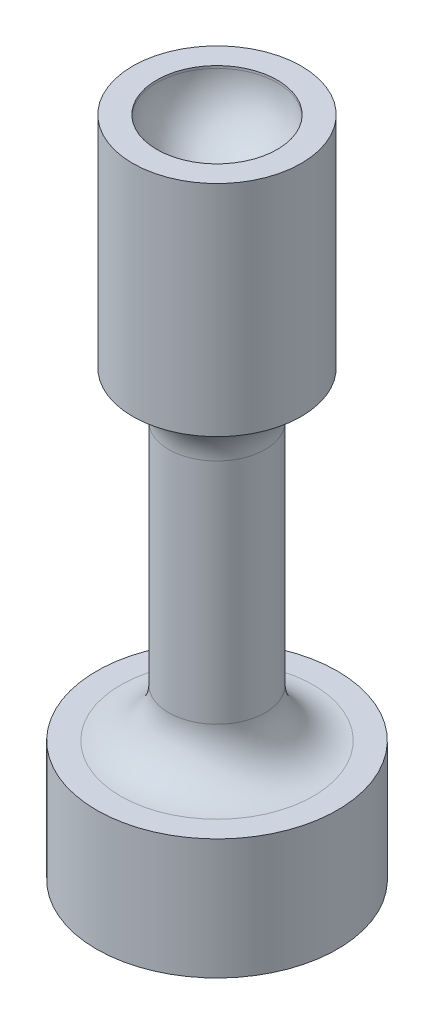
SolidWorks part; units mm, degrees
ref_plane "Front Plane" through (0, 0, 0) normal (0, 0, 1) x (1, 0, 0)
ref_plane "Top Plane" through (0, 0, 0) normal (0, 1, 0) x (1, 0, 0)
ref_plane "Right Plane" through (0, 0, 0) normal (1, 0, 0) x (0, 0, -1)
sketch "Sketch1" plane through (0, 0, 0) normal (0, 1, 0) x (1, 0, 0)
  circle A0 centre (0, 0) radius 5
  dimension "D1" = 10
extrude "Boss-Extrude1" add sketch "Sketch1" along normal blind 27.5
sketch "Sketch2" plane through (0, 0, 0) normal (0, -1, 0) x (1, 0, 0)
  line L1 (-2.0543, 3.4804) -> (-4.0413, -0.0388)
  line L2 (-4.0413, -0.0388) -> (-1.987, -3.5193)
  line L3 (-1.987, -3.5193) -> (2.0543, -3.4804)
  line L4 (2.0543, -3.4804) -> (4.0413, 0.0388)
  line L5 (4.0413, 0.0388) -> (1.987, 3.5193)
  line L6 (1.987, 3.5193) -> (-2.0543, 3.4804)
  circle A0 centre (0, 0) radius 3.5 construction
  dimension "D1" = 7
sketch "Sketch11" plane through (0, 27.5, 0) normal (0, 1, 0) x (1, 0, 0)
  circle A0 centre (0, 0) radius 2.5
  dimension "D1" = 5
extrude "Cut-Extrude3" cut sketch "Sketch11" against normal blind 0.1 contours A0
dome "Dome2" faces to dome 1 distance 2.5 reverse direction yes elliptical dome yes face at (0, 27.4, 2.5) parameters "D1"=2.5
sketch "Sketch12" plane through (0, 27.5, 0) normal (0, 1, 0) x (1, 0, 0)
  circle A0 centre (0, 0) radius 3.5
  circle A3 centre (0, 0) radius 5
  circle A4 centre (0, 0) radius 5
  dimension "D1" = 7
  dimension "D2" = 0
extrude "Cut-Extrude4" cut sketch "Sketch12" against normal blind 22.5
extrude "Cut-Extrude5" cut sketch "Sketch2" against normal blind 3
sketch "Sketch14" plane through (0, 0, 0) normal (0, 0, 1) x (1, 0, 0)
  line L0 (3.5, 5) -> (3.5, 27.5) construction
  line L1 (2, 5) -> (5, 5)
  line L2 (2, 5) -> (2, 18.4)
  line L3 (2, 18.4) -> (5, 18.4)
  line L4 (5, 5) -> (5, 18.4)
  line L5 (2, 5) -> (5, 18.4) construction
  line L6 (2, 18.4) -> (5, 5) construction
  line L7 (5, 5) -> (-5, 5) construction
  line L8 (0, 0) -> (0, 27.5) construction
  line L9 (2.5, 27.5) -> (-2.5, 27.5) construction
  point P0 (3.5, 11.7)
  dimension "D1" = 13.4
  dimension "D2" = 3
revolve "Cut-Revolve1" cut sketch "Sketch14" angle 360 about L8
fillet "Fillet2" radius 2 1 edges at (0, 5, -2)
fillet "Fillet3" radius 2 1 edges at (0, 18.4, -2)
